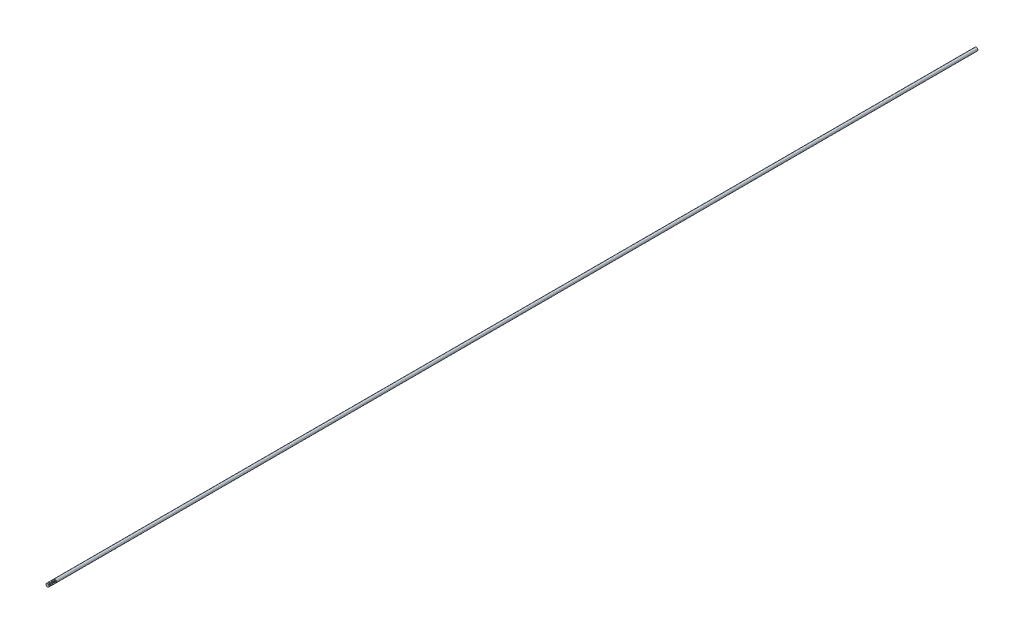
SolidWorks part; units mm, degrees
ref_plane "Front Plane" through (0, 0, 0) normal (0, 0, 1) x (1, 0, 0)
ref_plane "Top Plane" through (0, 0, 0) normal (0, 1, 0) x (1, 0, 0)
ref_plane "Right Plane" through (0, 0, 0) normal (1, 0, 0) x (0, 0, -1)
sketch "Sketch1" plane through (0, 0, 0) normal (0, 0, 1) x (1, 0, 0)
  circle A0 centre (0, 0) radius 3.175
  dimension "D1" = 6.35
extrude "Boss-Extrude1" add sketch "Sketch1" along normal blind 1828.8
thread "Thread1" pitch 1.27 method cut profile "Thread Profile1" start angle 0, offset 1, length 0, pitch 1.27, diameter 6.35
ref_plane "Plane1" through (-3.175, 0, 1829.8) normal (0, -1, 0) x (-1, 0, 0)
sketch "Thread Profile1" plane through (-3.175, 0, 1829.8) normal (0, -1, 0) x (-1, 0, 0)
  line L0 (0, 0) -> (0, 1.27) construction
  line L11 (0, 0) -> (0, 1.1112)
  line L12 (0, 1.1112) -> (-0.6874, 0.7144)
  line L13 (-0.6874, 0.7144) -> (-0.6874, 0.3969)
  line L15 (-0.6874, 0.3969) -> (0, 0)
  line L17 (-0.6874, 0.5556) -> (0, 0.5556) construction
  point P2 (0, 0)
  dimension "Pitch" = 1.27
  dimension "Profile_Angle" = 60
  dimension "Profile_Land" = 0.3175
  dimension "Profile_Height" = 0.6874
